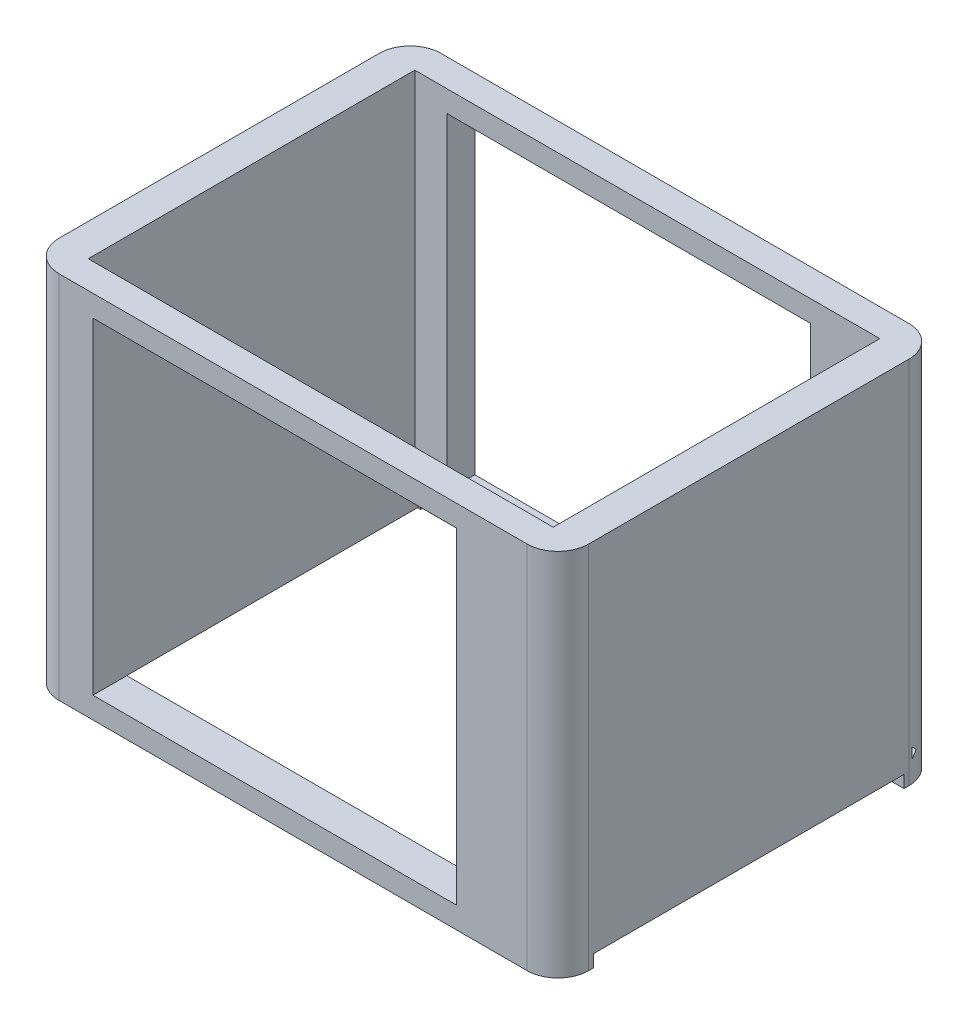
SolidWorks part; units mm, degrees
ref_plane "前视基准面" through (0, 0, 0) normal (0, 0, 1) x (1, 0, 0)
ref_plane "上视基准面" through (0, 0, 0) normal (0, 1, 0) x (1, 0, 0)
ref_plane "右视基准面" through (0, 0, 0) normal (1, 0, 0) x (0, 0, -1)
other "Configuration Table"
sketch "草图1" plane through (0, 0, 0) normal (0, 1, 0) x (1, 0, 0)
  line L1 (-43, -31) -> (43, -31)
  line L2 (-43, -31) -> (-43, 31)
  line L3 (-43, 31) -> (43, 31)
  line L4 (43, -31) -> (43, 31)
  line L5 (-43, -31) -> (43, 31) construction
  line L6 (-43, 31) -> (43, -31) construction
  line L7 (35.5, -25.5) -> (-35.5, -25.5)
  line L8 (35.5, -25.5) -> (35.5, 25.5)
  line L9 (35.5, 25.5) -> (-35.5, 25.5)
  line L10 (-35.5, -25.5) -> (-35.5, 25.5)
  line L11 (35.5, -25.5) -> (-35.5, 25.5) construction
  line L12 (35.5, 25.5) -> (-35.5, -25.5) construction
  point P0 (0, 0)
  point P5 (0, 0)
  dimension "D1" = 62
  dimension "D2" = 86
  dimension "D3" = 71
  dimension "D4" = 51
extrude "凸台-拉伸1" add sketch "草图1" along normal blind 60
sketch "草图2" plane through (0, 60, 0) normal (0, 1, 0) x (1, 0, 0)
  line L2 (-37.75, -26.515) -> (37.75, -26.515)
  line L3 (-37.75, -26.515) -> (-37.75, 26.515)
  line L4 (-37.75, 26.515) -> (37.75, 26.515)
  line L5 (37.75, -26.515) -> (37.75, 26.515)
  line L6 (-37.75, -26.515) -> (37.75, 26.515) construction
  line L7 (-37.75, 26.515) -> (37.75, -26.515) construction
  point P2 (0, 0)
  dimension "D1" = 53.03
  dimension "D2" = 75.5
extrude "切除-拉伸1" cut sketch "草图2" against normal blind 56.5
sketch "草图3" plane through (-37.75, 0, 0) normal (1, 0, 0) x (0, 0, -1)
  line L0 (26.515, 3.5) -> (-26.515, 60)
  line L1 (-26.515, 60) -> (-26.515, 3.5)
  line L2 (-26.515, 3.5) -> (26.515, 3.5)
extrude "凸台-拉伸2" add sketch "草图3" along normal blind 76
sketch "草图4" plane through (0, 0, 31) normal (0, 0, 1) x (1, 0, 0)
  line L0 (-43, 30) -> (43, 30) construction
  line L1 (-43, 60) -> (-43, 0) construction
  line L2 (43, 60) -> (43, 0) construction
  line L3 (43, 30) -> (0, 0) construction
  line L4 (0, 0) -> (0, 60) construction
  line L5 (-43, 60) -> (43, 60) construction
  line L7 (26.5, 3.485) -> (-32.5, 3.485)
  line L8 (26.5, 3.485) -> (26.5, 56.515)
  line L9 (26.5, 56.515) -> (-32.5, 56.515)
  line L10 (-32.5, 3.485) -> (-32.5, 56.515)
  line L11 (26.5, 3.485) -> (-32.5, 56.515) construction
  line L12 (26.5, 56.515) -> (-32.5, 3.485) construction
  point P12 (-3, 30)
  point P16 (0, 0)
  dimension "D1" = 59
  dimension "D2" = 53.03
  dimension "D3" = 10.5
extrude "切除-拉伸2" cut sketch "草图4" against normal through all
sketch "草图5" plane through (26.5, 0, 0) normal (-1, 0, 0) x (0, 0, 1)
  line L0 (-26.515, 3.5) -> (-27.3635, 4.3485)
  line L1 (-26.515, 56.515) -> (-26.515, 3.5) construction
  line L2 (-27.3635, 4.3485) -> (-26.515, 5.1971)
  line L3 (-26.515, 5.1971) -> (-26.515, 3.5)
  dimension "D1" = 45
  dimension "D2" = 1.2
  dimension "D3" = 90
extrude "切除-拉伸3" cut sketch "草图5" against normal through all both and the other way through all
sketch "草图7" plane through (0, 0, 0) normal (0, -1, 0) x (1, 0, 0)
  line L0 (-43, -31) -> (-43, 31) construction
  line L1 (43, -25.2) -> (-43, -25.2)
  line L2 (43, -25.2) -> (43, 25.2)
  line L3 (43, 25.2) -> (-43, 25.2)
  line L4 (-43, -25.2) -> (-43, 25.2)
  line L5 (43, -25.2) -> (-43, 25.2) construction
  line L6 (43, 25.2) -> (-43, -25.2) construction
  point P0 (0, 0)
  dimension "D1" = 50.4
extrude "切除-拉伸4" cut sketch "草图7" against normal blind 2
fillet "圆角1" radius 5 4 edges at (-43, 30, -31) (43, 30, -31) (43, 30, 31) (-43, 30, 31)
fillet "圆角2" radius 3 2 edges at (32.125, 5.1971, -26.515) (-35.125, 5.1971, -26.515)
